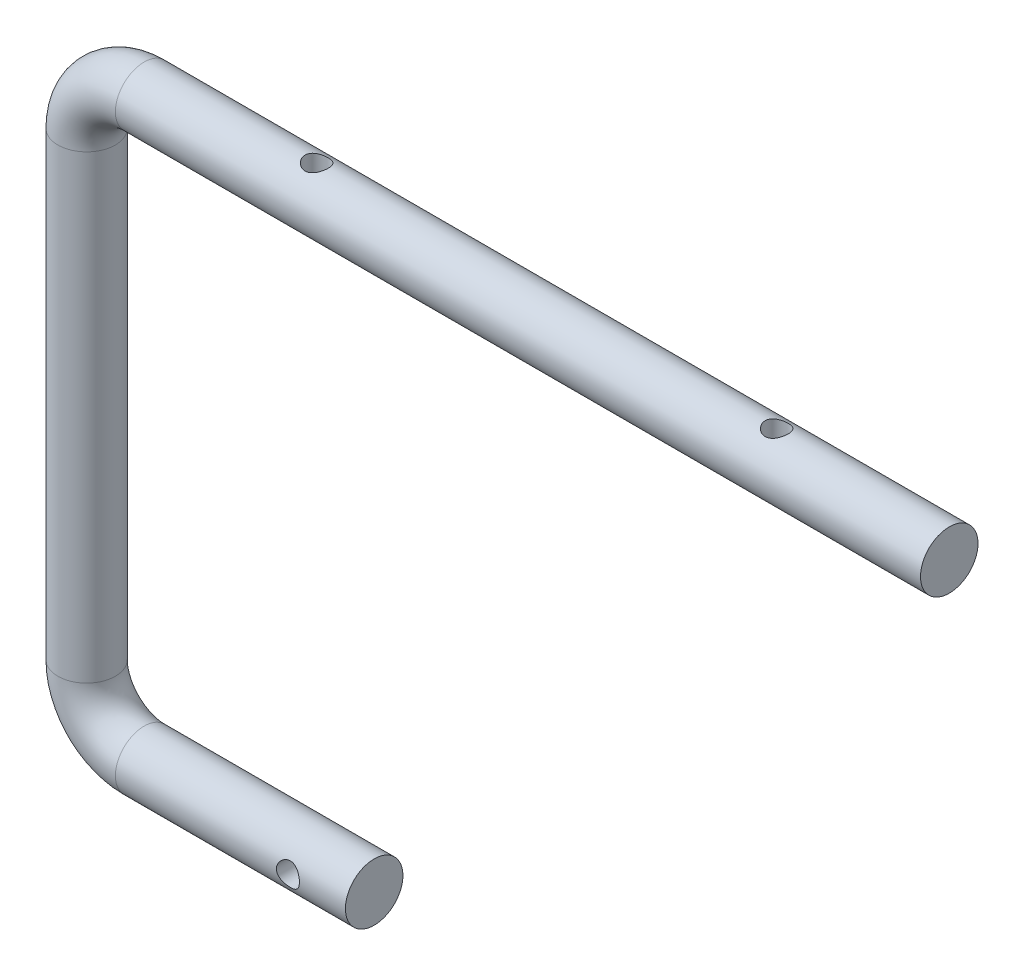
SolidWorks part; units mm, degrees
ref_plane "前视基准面" through (0, 0, 0) normal (0, 0, 1) x (1, 0, 0)
ref_plane "上视基准面" through (0, 0, 0) normal (0, 1, 0) x (1, 0, 0)
ref_plane "右视基准面" through (0, 0, 0) normal (1, 0, 0) x (0, 0, -1)
sketch "草图1" plane through (0, 0, 0) normal (0, 0, 1) x (1, 0, 0)
  line L0 (0, 0) -> (-40, 0)
  line L1 (-50, 10) -> (-50, 90)
  line L2 (-40, 100) -> (100, 100)
  arc A0 (-40, 0) -> (-50, 10) centre (-40, 10) cw
  arc A1 (-40, 100) -> (-50, 90) centre (-40, 90) ccw
  point P6 (-50, 0)
  point P9 (-50, 100)
  dimension "D4" = 10
  dimension "D1" = 50
  dimension "D2" = 100
  dimension "D3" = 150
sketch "草图3" plane through (0, 0, 0) normal (1, 0, 0) x (0, 0, -1)
  circle A0 centre (0, 0) radius 5
  dimension "D1" = 10
sweep "扫描1" add profiles "草图3" path "草图1"
sketch "草图4" plane through (0, 0, 0) normal (0, 0, 1) x (1, 0, 0)
  line L0 (0, 0) -> (-10, 0) construction
  line L1 (0, -5) -> (0, 5) construction
  circle A0 centre (-10, 0) radius 2
  dimension "D2" = 4
  dimension "D1" = 10
extrude "切除-拉伸1" cut sketch "草图4" against normal blind 10 and the other way blind 10
ref_plane "基准面1" through (0, 70, 0) normal (0, 1, 0) x (1, 0, 0)
sketch "草图6" plane through (0, 70, 0) normal (0, 1, 0) x (1, 0, 0)
  line L0 (100, 0) -> (70, 0) construction
  line L1 (100, -5) -> (100, 5) construction
  line L2 (70, 0) -> (-10, 0) construction
  circle A0 centre (70, 0) radius 2
  circle A1 centre (-10, 0) radius 2
  dimension "D3" = 4
  dimension "D4" = 4
  dimension "D1" = 30
  dimension "D2" = 80
extrude "切除-拉伸3" cut sketch "草图6" along normal blind 129
